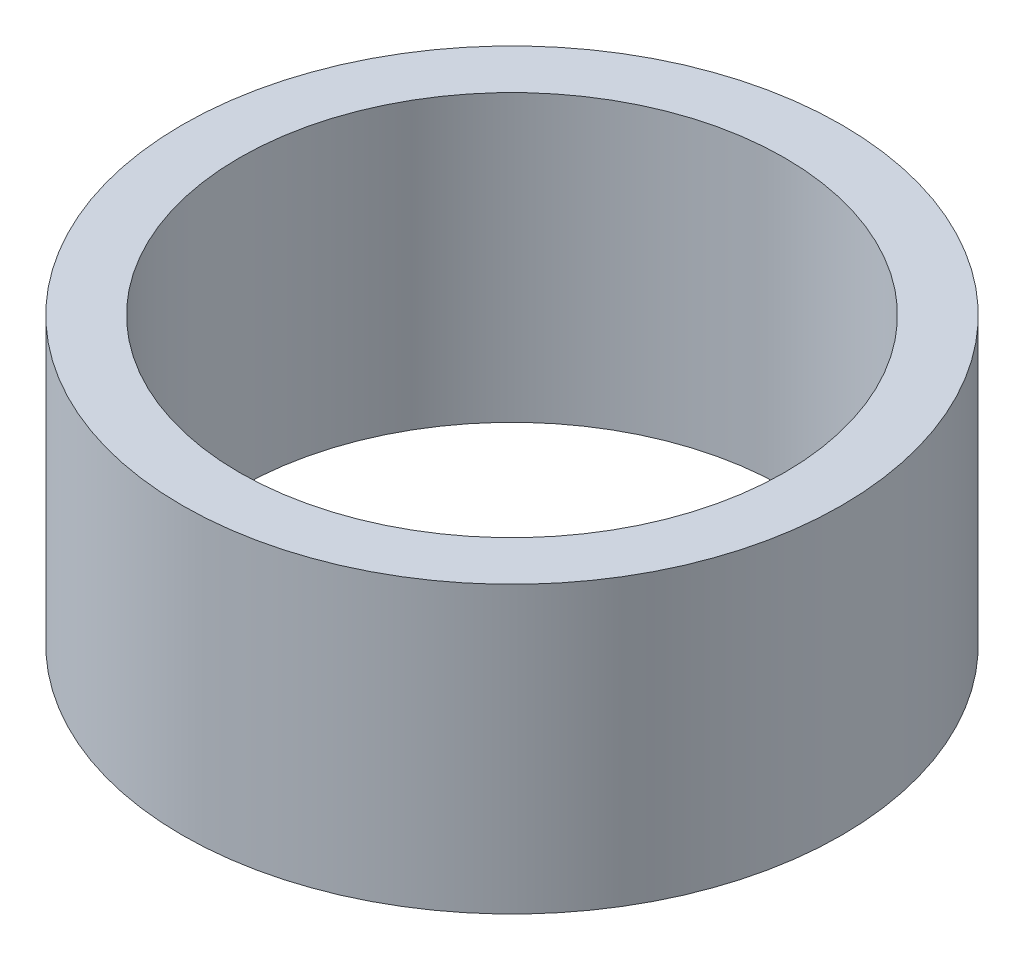
SolidWorks part; units mm, degrees
material "PETG"
ref_plane "Спереди" through (0, 0, 0) normal (0, 0, 1) x (1, 0, 0)
ref_plane "Сверху" through (0, 0, 0) normal (0, 1, 0) x (1, 0, 0)
ref_plane "Справа" through (0, 0, 0) normal (1, 0, 0) x (0, 0, -1)
sketch "Эскиз1" plane through (0, 0, 0) normal (0, 1, 0) x (1, 0, 0)
  circle A0 centre (0, 0) radius 5.25
  circle A1 centre (0, 0) radius 6.35
  dimension "D1" = 12.7
  dimension "D2" = 10.5
extrude "Бобышка-Вытянуть1" add sketch "Эскиз1" along normal blind 5.5
